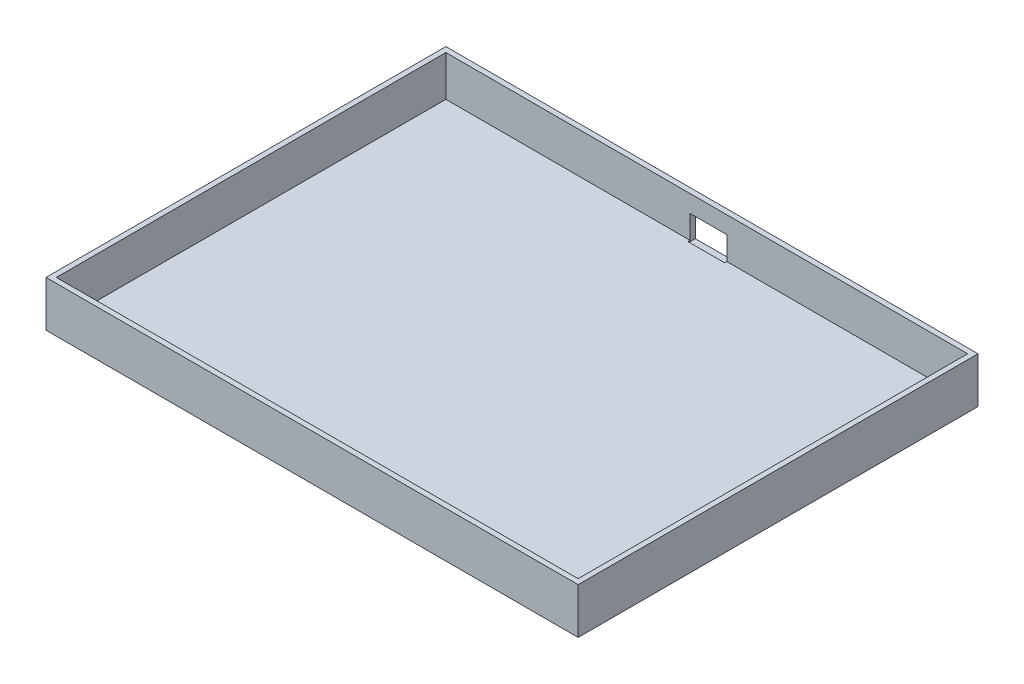
SolidWorks part; units mm, degrees
ref_plane "Front Plane" through (0, 0, 0) normal (0, 0, 1) x (1, 0, 0)
ref_plane "Top Plane" through (0, 0, 0) normal (0, 1, 0) x (1, 0, 0)
ref_plane "Right Plane" through (0, 0, 0) normal (1, 0, 0) x (0, 0, -1)
sketch "Sketch1" plane through (0, 0, 0) normal (0, 1, 0) x (1, 0, 0)
  line L1 (-1307.5, -982.5) -> (1307.5, -982.5)
  line L2 (-1307.5, -982.5) -> (-1307.5, 982.5)
  line L3 (-1307.5, 982.5) -> (1307.5, 982.5)
  line L4 (1307.5, -982.5) -> (1307.5, 982.5)
  line L5 (-1307.5, -982.5) -> (1307.5, 982.5) construction
  line L6 (-1307.5, 982.5) -> (1307.5, -982.5) construction
  point P0 (0, 0)
  dimension "D1" = 1965
  dimension "D2" = 2615
extrude "Boss-Extrude1" add sketch "Sketch1" along normal blind 260
shell "Shell1" thickness 25.4
sketch "Sketch2" plane through (0, 260, 0) normal (0, 1, 0) x (1, 0, 0)
  line L1 (1307.5, -982.5) -> (-1307.5, -982.5)
  line L2 (1307.5, -982.5) -> (1307.5, 982.5)
  line L3 (1307.5, 982.5) -> (-1307.5, 982.5)
  line L4 (-1307.5, -982.5) -> (-1307.5, 982.5)
  line L5 (1307.5, -982.5) -> (-1307.5, 982.5) construction
  line L6 (1307.5, 982.5) -> (-1307.5, -982.5) construction
  point P0 (0, 0)
extrude "Cut-Extrude1" cut sketch "Sketch2" against normal blind 35.306
sketch "Sketch3" plane through (0, 0, -982.5) normal (0, 0, -1) x (-1, 0, 0)
  line L0 (-1307.5, 0) -> (1307.5, 0) construction
  line L1 (81.649, 20) -> (-98.351, 20)
  line L2 (81.649, 20) -> (81.649, 140)
  line L3 (81.649, 140) -> (-98.351, 140)
  line L4 (-98.351, 20) -> (-98.351, 140)
  line L5 (81.649, 20) -> (-98.351, 140) construction
  line L6 (81.649, 140) -> (-98.351, 20) construction
  point P0 (-8.351, 80)
  dimension "D1" = 120
  dimension "D2" = 180
  dimension "D3" = 20
extrude "Cut-Extrude2" cut sketch "Sketch3" against normal blind 36
